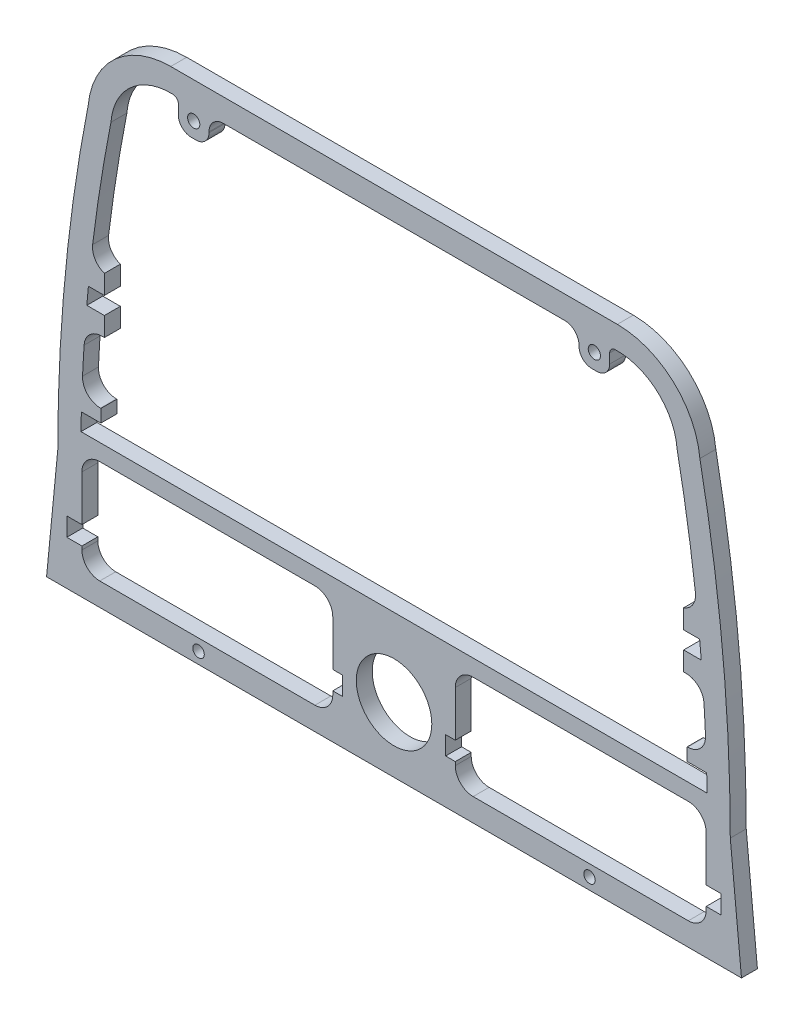
SolidWorks part; units mm, degrees
material "Delrin 2700 NC010, Low Viscosity Acetal Copolymer (SS)"
ref_plane "Front Plane" through (0, 0, 0) normal (0, 0, 1) x (1, 0, 0)
ref_plane "Top Plane" through (0, 0, 0) normal (0, 1, 0) x (1, 0, 0)
ref_plane "Right Plane" through (0, 0, 0) normal (1, 0, 0) x (0, 0, -1)
sketch "Sketch1" plane through (0, 0, 0) normal (0, 0, 1) x (1, 0, 0)
  line L0 (33.467, -10.7241) -> (34.5821, -22.225)
  line L1 (22.225, 27.94) -> (-22.225, 27.94)
  line L2 (-34.5821, -22.225) -> (-30.4415, 20.4816) construction
  line L3 (-33.467, -10.7241) -> (-33.467, 14.6458) construction
  line L4 (-33.467, -10.7241) -> (-34.5821, -22.225)
  line L5 (16.9823, 25.654) -> (-16.9823, 25.654)
  line L6 (31.0664, -9.652) -> (31.0664, -15.9702)
  line L7 (-31.0664, -19.939) -> (-18.6574, -19.939)
  line L8 (-34.5821, -22.225) -> (34.5821, -22.225)
  line L9 (-31.0664, -9.652) -> (-31.0664, -15.9703)
  line L10 (-18.415, 24.2213) -> (-18.415, 24.13)
  line L11 (-19.685, 22.86) -> (-20.193, 22.86)
  line L12 (-21.463, 24.13) -> (-21.463, 25.0906)
  line L13 (18.415, 24.2213) -> (18.415, 24.13)
  line L14 (19.685, 22.86) -> (20.193, 22.86)
  line L15 (21.463, 24.13) -> (21.463, 25.0906)
  line L16 (31.0788, -5.0038) -> (29.1738, -5.0038)
  line L17 (29.1738, -5.0038) -> (29.1738, -6.2738)
  line L18 (0, 18.415) -> (0, -18.415) construction
  line L19 (-30.4169, 4.9022) -> (-28.8263, 4.9022)
  line L20 (29.1738, -6.2738) -> (31.1192, -6.2738)
  line L21 (-20.2576, -19.939) -> (-6.096, -19.939)
  line L22 (22.225, 25.654) -> (-22.225, 25.654) construction
  line L23 (-31.181, -10.8343) -> (-32.0637, -19.939) construction
  line L24 (30.7313, 1.27) -> (28.8263, 1.27)
  line L25 (28.8263, 1.27) -> (28.8263, 3.175)
  line L26 (28.8263, 3.175) -> (30.5768, 3.175)
  line L27 (30.4169, 4.9022) -> (28.8263, 4.9022)
  line L28 (6.096, -19.939) -> (20.2576, -19.939)
  line L29 (-32.0637, -19.939) -> (32.0637, -19.939) construction
  line L30 (18.6574, -19.939) -> (31.679, -19.939)
  line L31 (31.181, -10.8343) -> (32.0637, -19.939) construction
  line L32 (28.8263, 4.9022) -> (28.8263, 6.8072)
  line L33 (28.8263, 6.8072) -> (30.2186, 6.8072)
  line L34 (-31.1579, -8.001) -> (31.1579, -8.001)
  line L35 (-6.096, -9.652) -> (-6.096, -15.9702)
  line L36 (-31.0664, -9.652) -> (-6.096, -9.652)
  line L37 (6.096, -9.652) -> (31.0664, -9.652)
  line L38 (-31.1579, -9.652) -> (31.1579, -9.652) construction
  line L39 (6.096, -9.652) -> (6.096, -15.9702)
  line L40 (18.415, 24.384) -> (19.939, 24.384) construction
  line L41 (19.939, 24.384) -> (21.463, 24.384) construction
  line L42 (19.939, 24.384) -> (19.939, 22.86) construction
  line L43 (19.939, 22.86) -> (19.939, 23.7744) construction
  line L44 (-28.8263, 4.9022) -> (-28.8263, 6.8072)
  line L45 (-28.8263, 6.8072) -> (-30.2186, 6.8072)
  line L46 (-29.1738, -6.2738) -> (-31.1192, -6.2738)
  line L47 (-29.1738, -5.0038) -> (-29.1738, -6.2738)
  line L48 (-31.0788, -5.0038) -> (-29.1738, -5.0038)
  line L49 (-28.8263, 3.175) -> (-30.5768, 3.175)
  line L50 (-28.8263, 1.27) -> (-28.8263, 3.175)
  line L51 (-30.7313, 1.27) -> (-28.8263, 1.27)
  line L52 (-6.096, -17.8117) -> (-6.096, -19.939)
  line L53 (-31.0664, -17.8118) -> (-31.0664, -19.939)
  line L54 (-31.0664, -17.8118) -> (-32.568, -17.8117)
  line L55 (-32.568, -15.9703) -> (-32.568, -17.8117)
  line L56 (31.0664, -17.8117) -> (32.568, -17.8117)
  line L57 (-32.568, -15.9703) -> (-32.568, -17.8117)
  line L58 (-31.0664, -15.9703) -> (-32.568, -15.9703)
  line L59 (31.0664, -15.9702) -> (32.568, -15.9702)
  line L60 (31.0664, -17.8117) -> (31.0664, -19.939)
  line L72 (-6.096, -17.8117) -> (-5.136, -17.8117)
  line L74 (-5.136, -17.8117) -> (-5.136, -15.9702)
  line L75 (-5.136, -15.9702) -> (-6.096, -15.9702)
  line L79 (32.568, -15.9702) -> (32.568, -17.8117)
  line L80 (6.096, -17.8117) -> (5.136, -17.8117)
  line L81 (5.136, -17.8117) -> (5.136, -15.9702)
  line L82 (5.136, -15.9702) -> (6.096, -15.9702)
  line L83 (6.096, -17.8117) -> (6.096, -19.939)
  line L85 (-19.4575, -19.939) -> (-19.4575, -22.225) construction
  line L86 (-20.2576, -19.939) -> (-18.6574, -19.939)
  line L87 (18.6574, -19.939) -> (20.2576, -19.939)
  arc A0 (22.225, 27.94) -> (30.4415, 20.4816) centre (22.225, 19.685) cw
  arc A1 (-22.225, 27.94) -> (-30.4415, 20.4816) centre (-22.225, 19.685) ccw
  arc A2 (33.467, -10.7241) -> (30.4415, 20.4816) centre (-128.9743, -10.7241) ccw
  circle A3 centre (0, -15.748) radius 3.7592
  circle A4 centre (19.4575, -21.082) radius 0.5715
  arc A5 (-33.467, -10.7241) -> (-30.4415, 20.4816) centre (128.9743, -10.7241) cw
  arc A7 (-20.193, 22.86) -> (-21.463, 24.13) centre (-20.193, 24.13) cw
  arc A8 (31.0788, -5.0038) -> (30.7313, 1.27) centre (-128.9743, -10.7241) ccw
  circle A9 centre (-19.939, 24.384) radius 0.6096
  circle A10 centre (19.939, 24.384) radius 0.6096
  circle A12 centre (-19.4575, -21.082) radius 0.5715
  arc A14 (-18.415, 24.13) -> (-19.685, 22.86) centre (-19.685, 24.13) cw
  arc A15 (-16.9823, 25.654) -> (-18.415, 24.2213) centre (-16.9823, 24.2213) ccw
  arc A16 (-21.463, 25.0906) -> (-22.0016, 25.6498) centre (-22.0226, 25.0906) ccw
  arc A17 (16.9823, 25.654) -> (18.415, 24.2213) centre (16.9823, 24.2213) cw
  arc A18 (-22.0016, 25.6498) -> (-28.1751, 20.1594) centre (-22.225, 19.685) ccw
  arc A19 (22.0016, 25.6498) -> (28.1751, 20.1594) centre (22.225, 19.685) cw
  arc A20 (31.181, -10.8343) -> (31.181, -10.7241) centre (-128.9743, -10.7241) ccw
  arc A21 (18.415, 24.13) -> (19.685, 22.86) centre (19.685, 24.13) ccw
  arc A22 (20.193, 22.86) -> (21.463, 24.13) centre (20.193, 24.13) ccw
  arc A23 (21.463, 25.0906) -> (22.0016, 25.6498) centre (22.0226, 25.0906) cw
  arc A24 (30.2186, 6.8072) -> (28.1751, 20.1594) centre (-128.9743, -10.7241) ccw
  arc A25 (30.5768, 3.175) -> (30.4169, 4.9022) centre (-128.9743, -10.7241) ccw
  arc A26 (-30.2186, 6.8072) -> (-28.1751, 20.1594) centre (128.9743, -10.7241) cw
  arc A27 (22.225, 25.654) -> (28.1751, 20.1594) centre (22.225, 19.685) cw construction
  arc A28 (-22.225, 25.654) -> (-28.1751, 20.1594) centre (-22.225, 19.685) ccw construction
  arc A29 (31.1579, -8.001) -> (31.1192, -6.2738) centre (-128.9743, -10.7241) ccw
  arc A30 (-31.181, -10.8343) -> (-28.1751, 20.1594) centre (128.9743, -10.7241) cw construction
  arc A31 (-30.5768, 3.175) -> (-30.4169, 4.9022) centre (128.9743, -10.7241) cw
  arc A32 (31.181, -10.8343) -> (28.1751, 20.1594) centre (-128.9743, -10.7241) ccw construction
  arc A33 (-31.1579, -8.001) -> (-31.1192, -6.2738) centre (128.9743, -10.7241) cw
  arc A34 (-31.0788, -5.0038) -> (-30.7313, 1.27) centre (128.9743, -10.7241) cw
  point P0 (0, 0)
  point P1 (0, 27.94)
  point P26 (0, -22.225)
  point P104 (-3.7592, -15.748)
  point P127 (-30.4335, -17.8117)
  dimension "D4" = 2.286
  dimension "D6" = 8.255
  dimension "D7" = 19.4575
  dimension "D8" = 50.165
  dimension "D9" = 6.477
  dimension "D5" = 1.2192
  dimension "D17" = 1.143
  dimension "D3" = 7.5184
  dimension "D19" = 1.27
  dimension "D20" = 1.27
  dimension "D31" = 0.5596
  dimension "D32" = 1.4327
  dimension "D2" = 44.45
  dimension "D11" = 1.27
  dimension "D12" = 69.1642
  dimension "D13" = 19.939
  dimension "D14" = 11.938
  dimension "D15" = 6.096
  dimension "D16" = 15.748
  dimension "D21" = 1.27
  dimension "D22" = 1.905
  dimension "D23" = 1.7272
  dimension "D24" = 2.4007
  dimension "D25" = 1.905
  dimension "D26" = 1.7272
  dimension "D27" = 11.176
  dimension "D28" = 1.651
  dimension "D30" = 0.508
  dimension "D29" = 27.432
extrude "Boss-Extrude1" add sketch "Sketch1" along normal blind 1.5875 contours A20 | A20 | A5 L4 L8 L0 A2 A0 L1 A1 A29 L34 A18 A16 L12 A7 L11 A14 L10 A15 L5 A17 L13 A21 L14 A22 L15 A23 A19 A24 L33 L32 L27 A25 L26 L25 L24 A8 L16 L17 L20 A12 L86 L7 L36 region at (33.1741, -16.557, 0)
ref_axis "Axis1" through (0, -15.748, 0) along (0, 0, 1)
fillet "Fillet1" radius 1.778 14 edges at (-31.0788, -5.0038, 0.7937) (-30.7313, 1.27, 0.7937) (-30.2186, 6.8072, 0.7937) (30.7313, 1.27, 0.7937) (30.2186, 6.8072, 0.7937) (31.0788, -5.0038, 0.7937) (-6.096, -9.652, 0.7937) (6.096, -9.652, 0.7937) (-6.096, -19.939, 0.7937) (6.096, -19.939, 0.7937) (31.0664, -19.939, 0.7937) (31.0664, -9.652, 0.7937) (-31.0664, -19.939, 0.7937) (-31.0664, -9.652, 0.7937)
